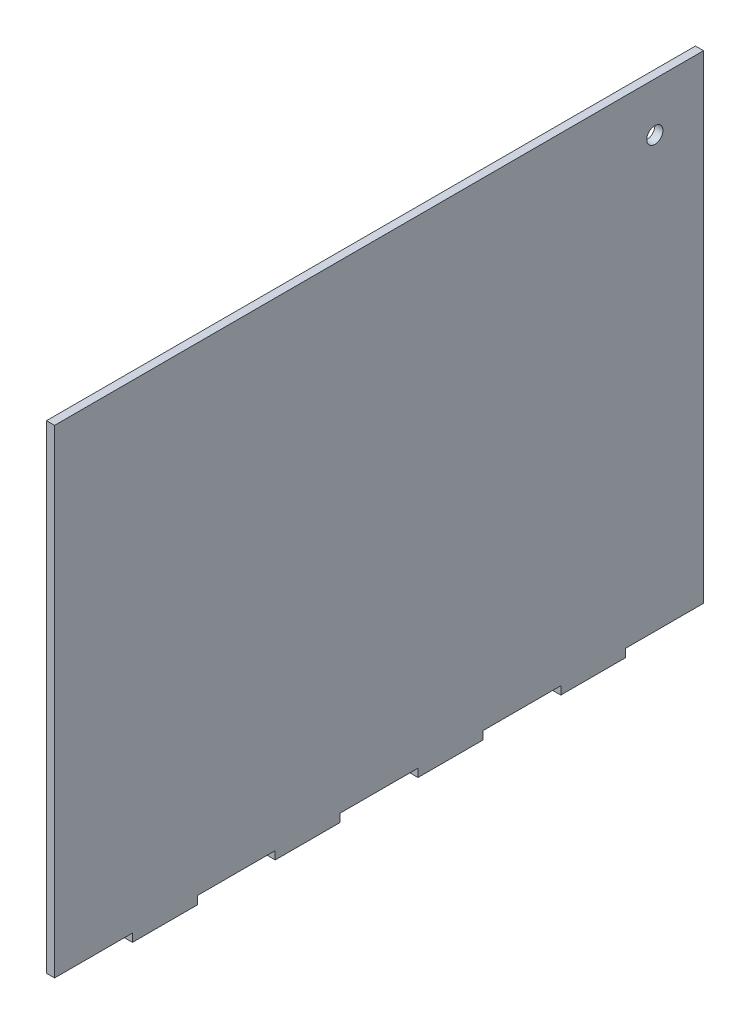
SolidWorks part; units mm, degrees
ref_plane "Front" through (0, 0, 0) normal (0, 0, 1) x (1, 0, 0)
ref_plane "Top" through (0, 0, 0) normal (0, 1, 0) x (1, 0, 0)
ref_plane "Right" through (0, 0, 0) normal (1, 0, 0) x (0, 0, -1)
sketch "Skizze1" plane through (0, 0, 0) normal (1, 0, 0) x (0, 0, -1)
  line L0 (200, 0) -> (-200, 0)
  line L1 (-200, 0) -> (-200, 300)
  line L2 (-200, 300) -> (200, 300)
  line L3 (0, 300) -> (0, 0) construction
  line L4 (200, 0) -> (200, 300)
  dimension "D1" = 400
  dimension "D2" = 300
extrude "Grundplatte" add sketch "Skizze1" along normal blind 5
sketch "Skizze2" plane through (5, 0, 0) normal (1, 0, 0) x (0, 0, -1)
  line L5 (-200, 0) -> (200, 0) construction
  line L11 (-200, 0) -> (-152, 0)
  line L12 (-200, 0) -> (-200, 5)
  line L13 (-200, 5) -> (-152, 5)
  line L14 (0, 0) -> (0, 300) construction
  line L15 (200, 300) -> (-200, 300) construction
  line L16 (-152, 0) -> (-152, 5)
  line L17 (-112, 0) -> (-64, 0)
  line L26 (-112, 0) -> (-112, 5)
  line L27 (-112, 5) -> (-64, 5)
  line L28 (-64, 0) -> (-64, 5)
  line L29 (-152, 5) -> (-112, 5) construction
  line L30 (-64, 5) -> (-24, 5) construction
  line L31 (24, 0) -> (-24, 0)
  line L32 (-24, 0) -> (-24, 5)
  line L34 (24, 0) -> (24, 5)
  line L35 (64, 5) -> (24, 5) construction
  line L36 (152, 5) -> (112, 5) construction
  line L37 (64, 0) -> (64, 5)
  line L38 (112, 5) -> (64, 5)
  line L39 (112, 0) -> (112, 5)
  line L40 (112, 0) -> (64, 0)
  line L41 (152, 0) -> (152, 5)
  line L42 (200, 5) -> (152, 5)
  line L43 (200, 0) -> (200, 5)
  line L44 (200, 0) -> (152, 0)
  line L45 (-24, 5) -> (0, 5) construction
  line L46 (-24, 5) -> (24, 5)
  point P14 (0, 7.2519)
  dimension "D1" = 48
  dimension "D2" = 5
  dimension "D3" = 40
extrude "Zapfen Boden" cut sketch "Skizze2" against normal through all
sketch "Skizze3" plane through (5, 0, 0) normal (1, 0, 0) x (0, 0, -1)
  line L0 (200, 5) -> (200, 300) construction
  line L1 (200, 300) -> (-200, 300) construction
  circle A0 centre (170, 270) radius 5
  dimension "D1" = 10
  dimension "D2" = 30
  dimension "D3" = 30
extrude "Verbindungsbohrungen" cut sketch "Skizze3" against normal through all
sketch "Skizze4" plane through (5, 0, 0) normal (1, 0, 0) x (0, 0, -1)
  line L0 (200, 152.5) -> (-200, 152.5) construction
  line L1 (200, 5) -> (200, 300) construction
  line L2 (-200, 300) -> (-200, 5) construction
  line L3 (195, 202.5) -> (195, 102.5)
  line L28 (200, 5) -> (195, 5)
  line L29 (200, 5) -> (200, 62.5)
  line L30 (200, 62.5) -> (195, 62.5)
  line L31 (195, 5) -> (195, 62.5)
  line L32 (195, 102.5) -> (200, 102.5)
  line L33 (200, 5) -> (200, 300) construction
  line L34 (200, 102.5) -> (200, 202.5)
  line L35 (195, 202.5) -> (200, 202.5)
  line L36 (195, 300) -> (195, 242.5)
  line L37 (200, 242.5) -> (195, 242.5)
  line L38 (200, 300) -> (200, 242.5)
  line L39 (200, 300) -> (195, 300)
  point P18 (195, 152.5)
  dimension "D1" = 5
  dimension "D2" = 40
  dimension "D3" = 100
extrude "Zapfen Seite" [suppressed] cut sketch "Skizze4" against normal through all
sketch "Skizze5" [suppressed] plane through (0, 0, 0) normal (-1, 0, 0) x (0, 0, 1)
  line L0 (0, 300) -> (0, 0) construction
  line L1 (-200, 300) -> (200, 300) construction
  line L2 (-200, 5) -> (-152, 5) construction
  line L3 (-200, 300) -> (-195, 300)
  line L4 (-200, 300) -> (-200, 5)
  line L5 (-200, 5) -> (-195, 5)
  line L6 (-195, 300) -> (-195, 5)
  dimension "D1" = 5
extrude "5mm Wandstärke Entfernnung" [suppressed] cut sketch "Skizze5" against normal through all
sketch "Skizze7" [suppressed] plane through (0, 0, 0) normal (-1, 0, 0) x (0, 0, 1)
  line L0 (-195, 5) -> (-195, 300) construction
  line L1 (-195, 300) -> (-200, 300)
  line L2 (-195, 300) -> (-195, 242.5)
  line L3 (-195, 242.5) -> (-200, 242.5)
  line L4 (-200, 300) -> (-200, 242.5)
  line L5 (-195, 202.5) -> (-200, 202.5)
  line L6 (-195, 202.5) -> (-195, 102.5)
  line L7 (-195, 102.5) -> (-200, 102.5)
  line L8 (-200, 202.5) -> (-200, 102.5)
  line L9 (-200, 152.5) -> (200, 152.5) construction
  line L10 (-195, 5) -> (-200, 5)
  line L11 (-195, 5) -> (-195, 62.5)
  line L12 (-195, 62.5) -> (-200, 62.5)
  line L13 (-200, 5) -> (-200, 62.5)
  line L14 (200, 300) -> (200, 5) construction
  dimension "D1" = 5
  dimension "D2" = 40
  dimension "D3" = 100
extrude "Aufsatz-Linear austragen2" [suppressed] add sketch "Skizze7" against normal up to surface (5 mm away) up to face at (5, 270, -175)
